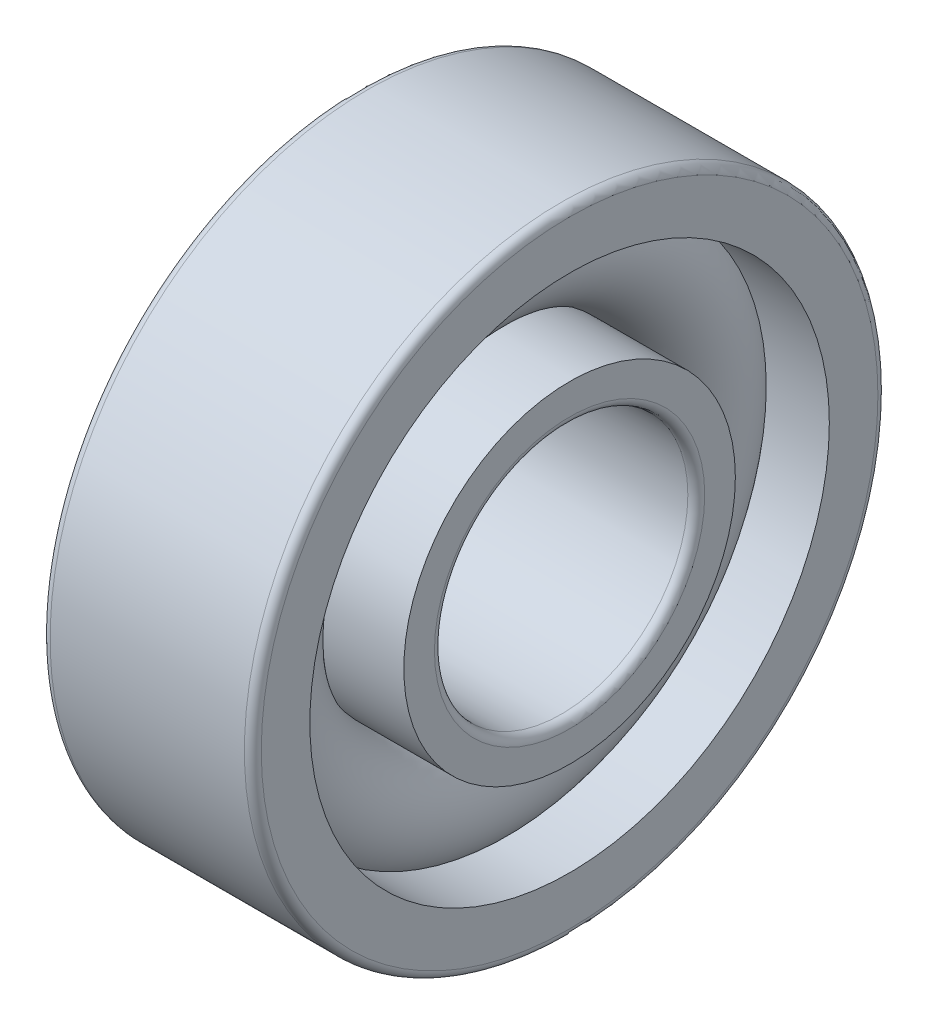
SolidWorks part; units mm, degrees
ref_plane "Plane1" through (0, 0, 0) normal (0, 0, 1) x (1, 0, 0)
ref_plane "Plane2" through (0, 0, 0) normal (0, 1, 0) x (1, 0, 0)
ref_plane "Plane3" through (0, 0, 0) normal (1, 0, 0) x (0, 0, -1)
other "Configuration Table"
sketch "Clipboard" plane through (0, 0, 0) normal (0, 0, 1) x (1, 0, 0)
  line L0 (-10, 0) -> (10, 0) construction
  line L1 (0, 0) -> (22.3471, -0.7804)
  line L2 (0, 0) -> (5.2468, 0.1832)
  line L3 (0, 0) -> (22.3471, -0.7804)
  line L4 (0, 0) -> (-22.3573, -0.3902)
sketch "CagSpiSke" plane through (0, 0, 0) normal (0, 0, 1) x (1, 0, 0)
  line L0 (0.3375, 5.025) -> (0.3375, 5.475)
  line L1 (0.3375, 5.475) -> (-0.3375, 5.475)
  line L2 (-0.3375, 5.475) -> (-0.3375, 5.025)
  line L3 (-0.3375, 5.025) -> (0.3375, 5.025)
  line L4 (-20.6375, 0) -> (20.6375, 0) construction
  line L5 (0, 0) -> (0, 23.7692) construction
revolve "CageSpine" add sketch "CagSpiSke" angle 0.001 about L4
ref_axis "Axis1" through (-50, 0, 0) along (1, 0, 0)
sketch "CagBalSke" plane through (0, 0, 0) normal (0, 0, 1) x (1, 0, 0)
  line L0 (-1.485, 5.25) -> (1.485, 5.25)
  line L1 (-1.905, 5.25) -> (1.905, 5.25) construction
  line L2 (-10, 0) -> (10, 0) construction
  line L3 (0, 0) -> (0, 24) construction
  arc A0 (1.485, 5.25) -> (-1.485, 5.25) centre (0, 5.25) cw
revolve "CageBall" [suppressed] add sketch "CagBalSke" angle 360 about L1 reverse direction yes
pattern_circular "CageBalls" [suppressed] count 2 every 180 about axis through (-50, 0, 0) along (1, 0, 0)
sketch "CagTrmODSke" plane through (0, 0, 0) normal (0, 0, 1) x (1, 0, 0)
  line L0 (1.486, 5.475) -> (1.486, 6.736)
  line L1 (1.486, 6.736) -> (-1.486, 6.736)
  line L2 (-1.486, 6.736) -> (-1.486, 5.475)
  line L3 (-1.486, 5.475) -> (1.486, 5.475)
  line L4 (-20.6375, 0) -> (20.6375, 0) construction
  line L5 (0, 0) -> (0, 25) construction
revolve "CageTrimOD" [suppressed] cut sketch "CagTrmODSke" angle 360 about L4 reverse direction yes
sketch "CagTrmIDSke" plane through (0, 0, 0) normal (0, 0, 1) x (1, 0, 0)
  line L0 (1.486, 3.766) -> (1.486, 5.025)
  line L1 (1.486, 5.025) -> (-1.486, 5.025)
  line L2 (-1.486, 5.025) -> (-1.486, 3.766)
  line L3 (-1.486, 3.766) -> (1.486, 3.766)
  line L4 (-20.6375, 0) -> (20.6375, 0) construction
  line L5 (0, 0) -> (0, 25) construction
revolve "CageTrimID" [suppressed] cut sketch "CagTrmIDSke" angle 360 about L4 reverse direction yes
sketch "BalSimSke" plane through (0, 0, 0) normal (0, 0, 1) x (1, 0, 0)
  line L0 (-10, 0) -> (10, 0) construction
  line L1 (-10, 5.25) -> (10, 5.25) construction
  line L2 (0, 0) -> (0, 23) construction
  circle A0 centre (0, 5.25) radius 1.35
revolve "BallsSimplified" add sketch "BalSimSke" angle 360 about L0
sketch "BalDetSke" plane through (0, 0, 0) normal (0, 0, 1) x (1, 0, 0)
  line L0 (-1.35, 5.25) -> (1.35, 5.25)
  line L1 (-1.905, 5.25) -> (1.905, 5.25) construction
  line L2 (0, 0) -> (0, 25) construction
  arc A0 (1.35, 5.25) -> (-1.35, 5.25) centre (0, 5.25) cw
revolve "BallDetailed" [suppressed] add sketch "BalDetSke" angle 360 about L1 reverse direction yes
sketch "InnRacSke" plane through (0, 0, 0) normal (0, 0, 1) x (1, 0, 0)
  line L0 (-0.9724, 4.35) -> (-2.5, 4.35)
  line L1 (-2.5, 4.35) -> (-2.5, 3.2)
  line L2 (-2.3, 3) -> (2.3, 3)
  line L3 (2.5, 3.2) -> (2.5, 3.925)
  line L4 (0, 3.925) -> (2.5, 3.925)
  line L5 (-20.6375, 0) -> (20.6375, 0) construction
  line L6 (0, 0) -> (0, 30) construction
  arc A0 (-2.5, 3.2) -> (-2.3, 3) centre (-2.3, 3.2) ccw
  arc A1 (2.3, 3) -> (2.5, 3.2) centre (2.3, 3.2) ccw
  arc A2 (0, 3.925) -> (-0.9724, 4.35) centre (0, 5.25) cw
revolve "InnerRace" add sketch "InnRacSke" angle 360 about L5 reverse direction yes
sketch "OutRacSke" plane through (0, 0, 0) normal (0, 0, 1) x (1, 0, 0)
  line L0 (0, 6.575) -> (-2.5, 6.575)
  line L1 (-2.5, 6.575) -> (-2.5, 7.3)
  line L2 (-2.3, 7.5) -> (2.3, 7.5)
  line L3 (2.5, 7.3) -> (2.5, 6.15)
  line L4 (2.5, 6.15) -> (0.9724, 6.15)
  line L5 (-20.6375, 0) -> (20.6375, 0) construction
  line L6 (0, 0) -> (0, 30) construction
  arc A0 (-2.5, 7.3) -> (-2.3, 7.5) centre (-2.3, 7.3) cw
  arc A1 (2.3, 7.5) -> (2.5, 7.3) centre (2.3, 7.3) cw
  arc A2 (0.9724, 6.15) -> (0, 6.575) centre (0, 5.25) ccw
revolve "OuterRace" add sketch "OutRacSke" angle 360 about L5 reverse direction yes
pattern_circular "BallsDetailed" [suppressed] count 2 every 180 about axis through (-50, 0, 0) along (1, 0, 0)
equation "\"BallCLRad@Clipboard\" = ( \"OD@OutRacSke\" + \"ID@InnRacSke\" ) / 4"
equation "\"BallCLRad@BalSimSke\" = \"BallCLRad@Clipboard\""
equation "\"BallCLRad@BalDetSke\" = \"BallCLRad@Clipboard\""
equation "\"BallCLRad@InnRacSke\" = \"BallCLRad@Clipboard\""
equation "\"BallCLRad@OutRacSke\" = \"BallCLRad@Clipboard\""
equation "\"Ball_diameter@InnRacSke\" = \"Ball_diameter@BalDetSke\" - 0.05"
equation "\"Ball_diameter@OutRacSke\" = \"Ball_diameter@BalDetSke\" - 0.05"
equation "\"Ball_diameter@BalSimSke\" = \"Ball_diameter@BalDetSke\""
equation "\"Width@OutRacSke\" = \"Width@InnRacSke\""
equation "\"Fillet_radius@OutRacSke\" = \"Fillet_radius@InnRacSke\""
equation "\"Max_count@Clipboard\" = int( 3.14159265 / atn(( \"Ball_diameter@BalDetSke\" / 2) / sqr( \"BallCLRad@Clipboard\"  *  \"BallCLRad@Clipboard\" - ( \"Ball_diameter@BalDetSke\" / 2) *  ( \"Ball_diameter@BalDetSke\" / 2))))"
equation "\"Max_count@Clipboard\" = ((sgn( \"Max_count@Clipboard\" - \"Count@Clipboard\" )-1)*( \"Max_count@Clipboard\" - \"Count@Clipboard\" ))/-2+ \"Count@Clipboard\""
equation "\"Count@BallsDetailed\" = int( \"Show_count@Clipboard\" ) "
equation "\"Count@BallsDetailed\" = ((sgn( \"Count@BallsDetailed\" - \"Max_count@Clipboard\" )-1)*( \"Count@BallsDetailed\" - \"Max_count@Clipboard\" ))/-2+ \"Max_count@Clipboard\""
equation "\"Count@BallsDetailed\" = ((sgn( \"Count@BallsDetailed\" - \"Min_count@Clipboard\" )+1)*( \"Count@BallsDetailed\" - \"Min_count@Clipboard\"))/2 +\"Min_count@Clipboard\""
equation "\"Angle@BallsDetailed\" = 360.0 / \"Max_count@Clipboard\""
equation "\"BallCLRad@CagBalSke\" = \"BallCLRad@Clipboard\""
equation "\"Count@CageBalls\" = \"Count@BallsDetailed\""
equation "\"Angle@CageBalls\" = \"Angle@BallsDetailed\""
equation "\"Angle@CageSpine\" =  \"Angle@CageBalls\" * ( \"Count@CageBalls\" -1 + int( \"Count@CageBalls\" / \"Max_count@Clipboard\" ) )  + 0.001 -  int( \"Count@CageBalls\" / \"Max_count@Clipboard\" ) * 0.001"
equation "\"Angle@CageSpine\" =  \"Angle@CageSpine\" * int( \"Min_count@Clipboard\" / 2) + int(1 / \"Min_count@Clipboard\")  * 0.001"
equation "\"CageWallOD@CagBalSke\" =  \"Ball_diameter@BalDetSke\" * 1.1"
equation "\"Thickness@CagSpiSke\" =  \"Ball_diameter@BalDetSke\" * 0.25"
equation "\"OD@CagTrmODSke\" = \"BallCLRad@Clipboard\" * 2 + \"CageWallOD@CagBalSke\" + 0.002"
equation "\"ID@CagTrmODSke\" = \"BallCLRad@Clipboard\" * 2 + \"Ball_diameter@BalDetSke\" / 6"
equation "\"OD@CagTrmIDSke\" = \"BallCLRad@Clipboard\" * 2 - \"Ball_diameter@BalDetSke\" / 6"
equation "\"ID@CagTrmIDSke\" = \"BallCLRad@Clipboard\" * 2 - \"CageWallOD@CagBalSke\" + 0.002"
equation "\"OD@CagSpiSke\" = \"ID@CagTrmODSke\""
equation "\"ID@CagSpiSke\" = \"OD@CagTrmIDSke\""
equation "\"Width@CagTrmODSke\" = \"CageWallOD@CagBalSke\" + 0.002"
equation "\"Width@CagTrmIDSke\" = \"CageWallOD@CagBalSke\" + 0.002"
